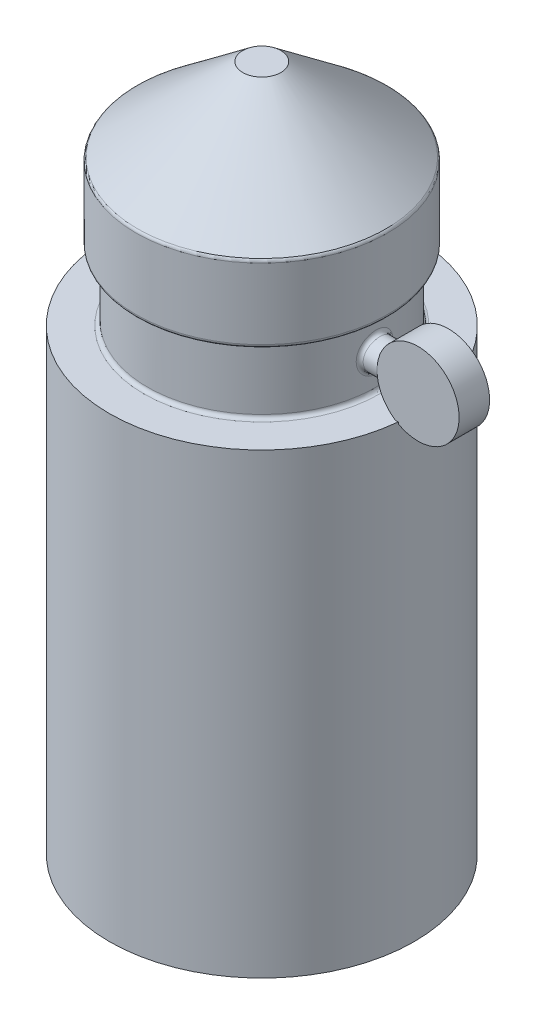
SolidWorks part; units mm, degrees
ref_plane "前视基准面" through (0, 0, 0) normal (0, 0, 1) x (1, 0, 0)
ref_plane "上视基准面" through (0, 0, 0) normal (0, 1, 0) x (1, 0, 0)
ref_plane "右视基准面" through (0, 0, 0) normal (1, 0, 0) x (0, 0, -1)
sketch "草图1" plane through (0, 0, 0) normal (0, 0, 1) x (1, 0, 0)
  line L0 (0, 0) -> (5, 0)
  line L1 (5, 0) -> (33, -22)
  line L2 (33, -22) -> (33, -42)
  line L3 (33, -42) -> (30, -42)
  line L4 (30, -42) -> (30, -60)
  line L5 (30, -60) -> (40, -60)
  line L6 (40, -60) -> (40, -180)
  line L7 (40, -180) -> (0, -180)
  line L8 (0, -180) -> (0, 0)
  dimension "D1" = 40
  dimension "D2" = 5
  dimension "D3" = 3
  dimension "D4" = 10
  dimension "D5" = 20
  dimension "D6" = 18
  dimension "D7" = 120
  dimension "D8" = 180
revolve "旋转1" add sketch "草图1" angle 360 about L8
sketch "草图2" plane through (0, 0, 0) normal (1, 0, 0) x (0, 0, -1)
  line L0 (0, -42) -> (0, -60) construction
  line L1 (-30, -42) -> (30, -42) construction
  line L2 (40, -60) -> (-40, -60) construction
  line L3 (0, -51) -> (30, -51) construction
  line L4 (30, -60) -> (30, -42) construction
  circle A0 centre (0, -51) radius 4
  dimension "D1" = 8
extrude "凸台-拉伸1" add sketch "草图2" along normal blind 35
sketch "草图3" plane through (0, 0, 0) normal (0, 0, 1) x (1, 0, 0)
  line L0 (35, -51) -> (45, -51) construction
  line L1 (35, -55) -> (35, -47) construction
  circle A0 centre (45, -51) radius 10.7703
  dimension "D1" = 10
extrude "凸台-拉伸2" add sketch "草图3" along normal blind 4 and the other way blind 4
fillet "圆角3" radius 1 5 edges at (29.7452, -50.1198, -3.9019) (0, -60, -30) (0, -42, -30) (0, -22, -33) (0, -42, -33)
